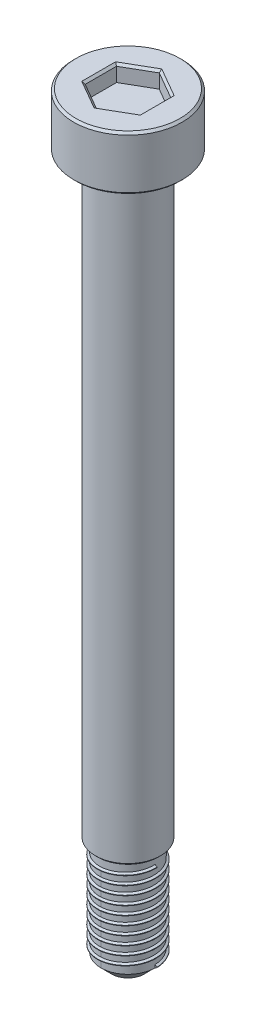
SolidWorks part; units mm, degrees
ref_plane "Front Plane" through (0, 0, 0) normal (0, 0, 1) x (1, 0, 0)
ref_plane "Top Plane" through (0, 0, 0) normal (0, 1, 0) x (1, 0, 0)
ref_plane "Right Plane" through (0, 0, 0) normal (1, 0, 0) x (0, 0, -1)
sketch "Sketch1" plane through (0, 0, 0) normal (0, 0, 1) x (1, 0, 0)
  line L0 (0, 92.3708) -> (0, 0) construction
  line L1 (0, 70) -> (5, 70)
  line L2 (5, 70) -> (5, 65)
  line L3 (5, 65) -> (2, 65)
  line L4 (2, 65) -> (2, 64)
  line L5 (2, 64) -> (3, 64)
  line L6 (3, 64) -> (3, 10)
  line L7 (2.5, 10) -> (3, 10)
  line L8 (2.5, 10) -> (2.5, 0)
  line L9 (2.5, 0) -> (0, 0)
  line L10 (0, 0) -> (0, 70)
  dimension "D1" = 54
  dimension "D2" = 10
  dimension "D3" = 6
  dimension "D4" = 5
  dimension "D5" = 10
  dimension "D6" = 5
  dimension "D7" = 1
  dimension "D8" = 4
revolve "Revolve1" add sketch "Sketch1" angle 360 about L0
sketch "Sketch2" plane through (0, 70, 0) normal (0, 1, 0) x (1, 0, 0)
  line L1 (0, 2.8868) -> (-2.5, 1.4434)
  line L2 (-2.5, 1.4434) -> (-2.5, -1.4434)
  line L3 (-2.5, -1.4434) -> (0, -2.8868)
  line L4 (0, -2.8868) -> (2.5, -1.4434)
  line L5 (2.5, -1.4434) -> (2.5, 1.4434)
  line L6 (2.5, 1.4434) -> (0, 2.8868)
  circle A0 centre (0, 0) radius 2.5 construction
  dimension "D1" = 5
extrude "Cut-Extrude1" cut sketch "Sketch2" against normal blind 1.5
chamfer "Chamfer1" distance 0.2 angle 45 7 edges at (0, 70, 5) (-2.5, 70, 0) (-1.25, 70, 2.1651) (1.25, 70, 2.1651) (2.5, 70, 0) (1.25, 70, -2.1651) (-1.25, 70, -2.1651)
chamfer "Chamfer2" distance 0.2 angle 45 2 edges at (0, 65, 2) (0, 65, 5)
chamfer "Chamfer3" distance 0.2 angle 45 2 edges at (0, 64, 3) (0, 64, 2)
chamfer "Chamfer4" distance 0.2 angle 45 2 edges at (0, 10, 2.5) (0, 10, 3)
chamfer "Chamfer5" distance 1 angle 45 1 edges at (0, 0, 2.5)
thread "Thread1" pitch 0.35 method extrude profile "Thread Profile1" start angle 0, offset 0, length 8, pitch 0.8, diameter 5
ref_plane "Plane1" through (2.5, 1, 0) normal (0, 0, 1) x (1, 0, 0)
sketch "Thread Profile1" plane through (2.5, 1, 0) normal (0, 0, 1) x (1, 0, 0)
  line L0 (0, 0) -> (0, 0.35) construction
  line L1 (0, 0) -> (0.1894, 0.1094)
  line L2 (0.1894, 0.1094) -> (0.1894, 0.1531)
  line L3 (0.1894, 0.1531) -> (0, 0.2625)
  line L4 (0.1894, 0.1312) -> (0, 0.1312) construction
  line L11 (0, 0) -> (0, 0.2625)
  point P2 (0, 0)
  dimension "Pitch" = 0.35
  dimension "Profile_Angle" = 60
  dimension "Profile_Land" = 0.0437
  dimension "Profile_Height" = 0.1894
